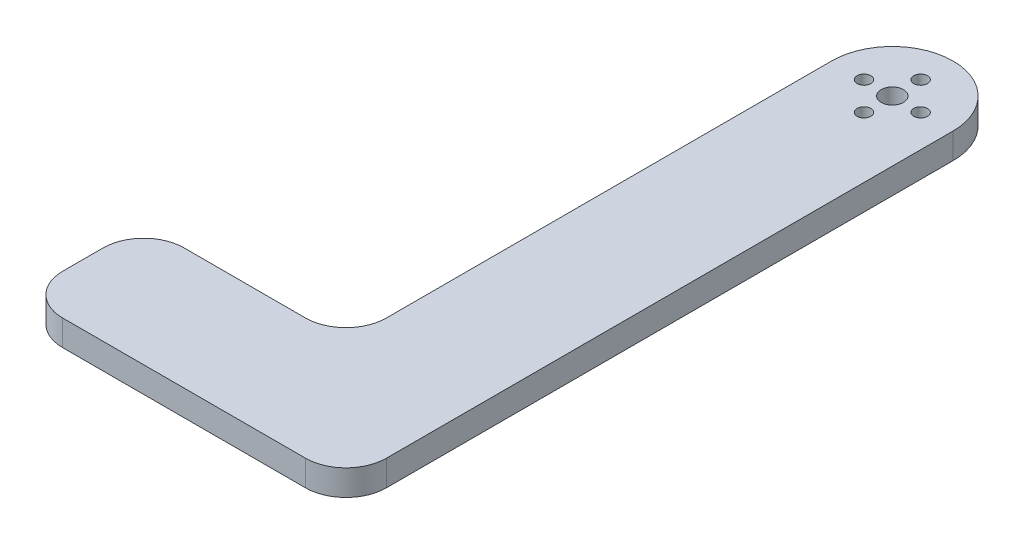
SolidWorks part; units mm, degrees
material "Pine"
ref_plane "Front Plane" through (0, 0, 0) normal (0, 0, 1) x (1, 0, 0)
ref_plane "Top Plane" through (0, 0, 0) normal (0, 1, 0) x (1, 0, 0)
ref_plane "Right Plane" through (0, 0, 0) normal (1, 0, 0) x (0, 0, -1)
sketch "Sketch2" plane through (0, 0, 0) normal (0, 1, 0) x (1, 0, 0)
  line L0 (-15, 0) -> (-15, -120)
  line L1 (-15, -120) -> (-65, -120)
  line L2 (-65, -120) -> (-65, -150)
  line L3 (-65, -150) -> (15, -150)
  line L4 (15, -150) -> (15, 0)
  circle A0 centre (0, 0) radius 15
  circle A1 centre (0, 0) radius 7 construction
  dimension "D1" = 30
  dimension "D2" = 14
  dimension "D3" = 30
  dimension "D4" = 50
  dimension "D5" = 150
extrude "Boss-Extrude1" add sketch "Sketch2" along normal blind 6.35 contours A0 L0 L1 L2 L3 L4 | A0 region at (-10.6259, 0, 95.2348) region at (0, 0, 0)
sketch "Sketch3" plane through (0, 6.35, 0) normal (0, 1, 0) x (1, 0, 0)
  circle A0 centre (0, 0) radius 7 construction
  circle A1 centre (0, 0) radius 7 construction
  point P3 (0, 7)
hole_wizard "M3 Clearance Hole1" positions "Sketch3" profile "Sketch4" hole size "M3" standard "ANSI Metric" end condition through all
sketch "Sketch4" plane through (0, 6.35, -7) normal (1, 0, 0) x (0, 0, 1)
  line L0 (0, 0) -> (0, 6.35)
  line L1 (0, 6.35) -> (1.7, 6.35)
  line L2 (1.7, 6.35) -> (1.7, 0)
  line L5 (1.7, 0) -> (0, 0)
  line L11 (0, -6.35) -> (0, 107.95) construction
  dimension "Thru Hole Dia." = 3.4
  dimension "Thru Hole Depth" = 6.35
pattern_circular "CirPattern1" count 4 over 360 about axis through (0, 6.35, 0) along (0, -1, 0) of "M3 Clearance Hole1" reverse direction yes
fillet "Fillet1" radius 10 4 edges at (15, 3.175, 150) (-65, 3.175, 150) (-65, 3.175, 120) (-15, 3.175, 120)
sketch "Sketch5" plane through (0, 6.35, 0) normal (0, 1, 0) x (1, 0, 0)
  circle A0 centre (0, 0) radius 2.75
  dimension "D1" = 5.5
extrude "Cut-Extrude1" cut sketch "Sketch5" against normal blind 10
